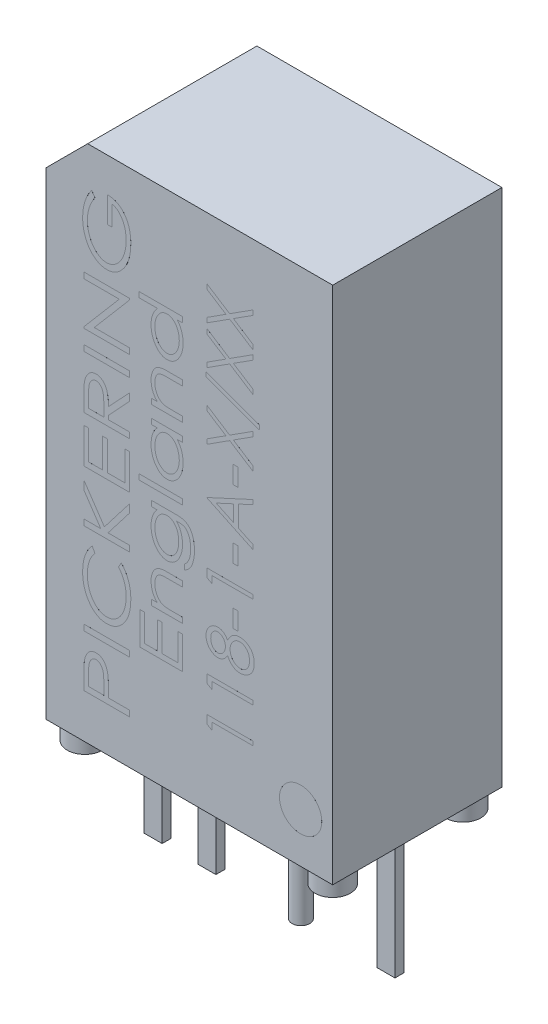
SolidWorks part; units mm, degrees
ref_plane "Front Plane" through (0, 0, 0) normal (0, 0, 1) x (1, 0, 0)
ref_plane "Top Plane" through (0, 0, 0) normal (0, 1, 0) x (1, 0, 0)
ref_plane "Right Plane" through (0, 0, 0) normal (1, 0, 0) x (0, 0, -1)
sketch "Sketch1" plane through (0, 0, 0) normal (0, 1, 0) x (1, 0, 0)
  line L1 (4.065, -2.4) -> (-4.065, -2.4)
  line L2 (4.065, -2.4) -> (4.065, 2.4)
  line L3 (4.065, 2.4) -> (-4.065, 2.4)
  line L4 (-4.065, -2.4) -> (-4.065, 2.4)
  line L5 (4.065, -2.4) -> (-4.065, 2.4) construction
  line L6 (4.065, 2.4) -> (-4.065, -2.4) construction
  point P0 (0, 0)
  dimension "D1" = 4.8
  dimension "D2" = 8.13
extrude "Main Body" add sketch "Sketch1" along normal blind 14.732
sketch "Sketch2" plane through (0, 0, 2.4) normal (0, 0, 1) x (1, 0, 0)
  line L0 (-2.885, 14.732) -> (-4.065, 13.552)
  line L1 (-4.065, 14.732) -> (4.065, 14.732) construction
  line L2 (-4.065, 14.732) -> (-4.065, 0) construction
  line L3 (-4.065, 13.552) -> (-4.065, 14.732)
  line L4 (-4.065, 14.732) -> (-2.885, 14.732)
  dimension "D1" = 6.95
  dimension "D2" = 45
extrude "Aesthetic cut" cut sketch "Sketch2" against normal through all
sketch "Sketch3" plane through (0, 0, 0) normal (0, -1, 0) x (1, 0, 0)
  line L0 (-4.065, 2.4) -> (4.065, 2.4) construction
  line L1 (-4.065, -2.4) -> (-4.065, 2.4) construction
  line L2 (4.065, -2.4) -> (-4.065, -2.4) construction
  line L3 (4.065, 2.4) -> (4.065, -2.4) construction
  circle A0 centre (-3.515, 1.85) radius 0.5
  circle A1 centre (-3.515, -1.85) radius 0.5
  circle A2 centre (3.515, 1.85) radius 0.5
  circle A3 centre (3.515, -1.85) radius 0.5
  dimension "D1" = 1
  dimension "D4" = 1
  dimension "D7" = 1
  dimension "D10" = 1
  dimension "D2" = 0.55
  dimension "D3" = 0.55
  dimension "D5" = 0.55
  dimension "D6" = 0.55
  dimension "D8" = 0.55
  dimension "D9" = 0.55
  dimension "D11" = 0.55
  dimension "D12" = 0.55
extrude "Feet" add sketch "Sketch3" along normal blind 0.508
sketch "Sketch4" plane through (0, 0, 0) normal (0, -1, 0) x (1, 0, 0)
  line L0 (-4.065, -2.4) -> (-4.065, 2.4) construction
  line L1 (-3.554, -0.127) -> (-3.046, -0.127)
  line L2 (-3.554, -0.127) -> (-3.554, 0.127)
  line L3 (-3.554, 0.127) -> (-3.046, 0.127)
  line L4 (-3.046, -0.127) -> (-3.046, 0.127)
  line L5 (-3.554, -0.127) -> (-3.046, 0.127) construction
  line L6 (-3.554, 0.127) -> (-3.046, -0.127) construction
  line L13 (-2.03, -0.127) -> (-1.522, -0.127)
  line L14 (-2.03, -0.127) -> (-2.03, 0.127)
  line L15 (-2.03, 0.127) -> (-1.522, 0.127)
  line L16 (-1.522, -0.127) -> (-1.522, 0.127)
  line L17 (-2.03, -0.127) -> (-1.522, 0.127) construction
  line L18 (-2.03, 0.127) -> (-1.522, -0.127) construction
  line L19 (3.05, -0.127) -> (3.558, -0.127)
  line L20 (3.05, -0.127) -> (3.05, 0.127)
  line L21 (3.05, 0.127) -> (3.558, 0.127)
  line L22 (3.558, -0.127) -> (3.558, 0.127)
  line L23 (3.05, -0.127) -> (3.558, 0.127) construction
  line L24 (3.05, 0.127) -> (3.558, -0.127) construction
  circle A0 centre (0.764, 0) radius 0.25
  point P0 (-3.3, 0)
  point P10 (-1.776, 0)
  point P15 (3.304, 0)
  dimension "D3" = 1.524
  dimension "D4" = 0.5
  dimension "D1" = 0.508
  dimension "D2" = 0.254
  dimension "D5" = 0.508
  dimension "D6" = 0.254
  dimension "D7" = 0.508
  dimension "D8" = 0.254
  dimension "D9" = 5.08
  dimension "D10" = 2.54
  dimension "D11" = 0.765
extrude "Pins" add sketch "Sketch4" along normal blind 3.678
sketch "Sketch5" plane through (0, 0, 2.4) normal (0, 0, 1) x (1, 0, 0)
  line L0 (-1.6944, 0.9898) -> (-1.6944, 13.9319) construction
  line L1 (1.8056, 0.9898) -> (1.8056, 13.9319) construction
  line L2 (-0.1944, 0.9898) -> (-0.1944, 13.9319) construction
  circle A0 centre (3.1553, 1.3988) radius 0.6
  text T0 "PICKERING" font "Century Gothic" height 1.3
  text T1 "England" font "Century Gothic" height 1.2
  text T2 "118-1-A-X/XX" font "Century Gothic" height 1.3
  dimension "D3" = 1.2
  dimension "D1" = 1.5
  dimension "D2" = 2
extrude "Lettering" add sketch "Sketch5" along normal blind 0.0001
ref_plane "Plane1" through (0, 0, 0) normal (0, 0, 1) x (1, 0, 0)
ref_plane "Plane2" through (-3.3, 0, 0) normal (-1, 0, 0) x (0, 0, 1)
ref_axis "Axis1" through (-3.3, -3.8619, 0) along (0, 1, 0)
